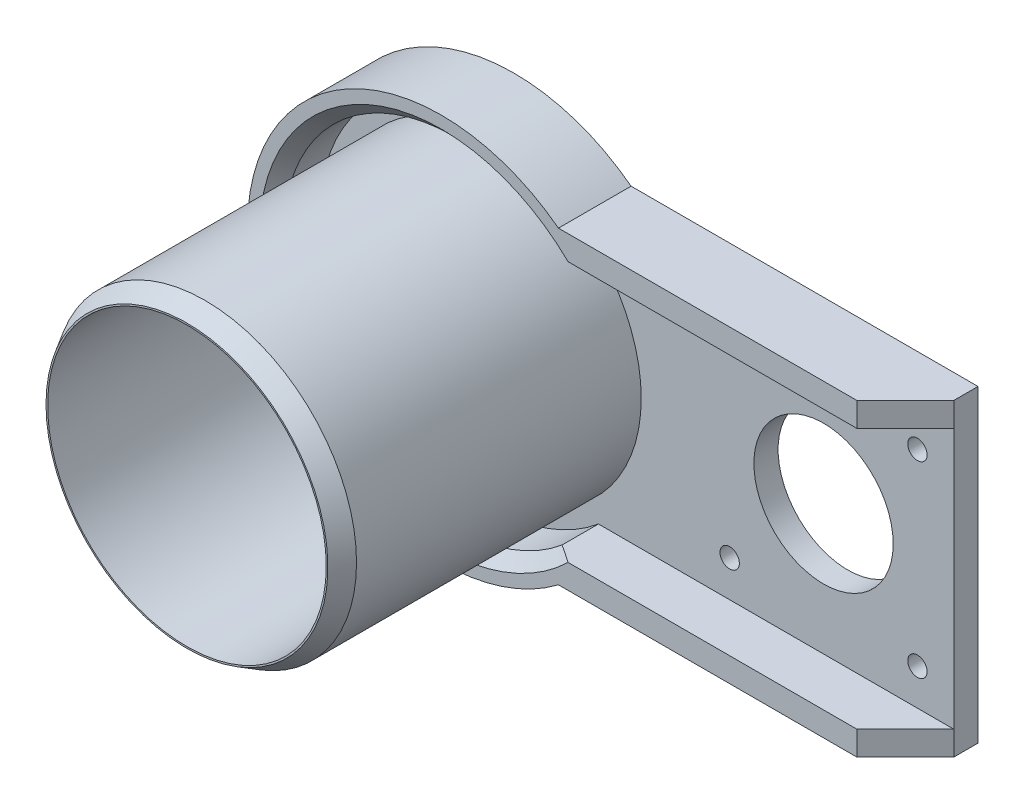
SolidWorks part; units mm, degrees
ref_plane "Front Plane" through (0, 0, 0) normal (0, 0, 1) x (1, 0, 0)
ref_plane "Top Plane" through (0, 0, 0) normal (0, 1, 0) x (1, 0, 0)
ref_plane "Right Plane" through (0, 0, 0) normal (1, 0, 0) x (0, 0, -1)
sketch "Sketch1" plane through (0, 0, 0) normal (0, 0, 1) x (1, 0, 0)
  line L0 (19.3326, 25.5) -> (76.6, 25.5)
  line L1 (76.6, 25.5) -> (76.6, -25.5)
  line L2 (76.6, -25.5) -> (19.3326, -25.5)
  circle A0 centre (0, 0) radius 6.55
  circle A1 centre (55.1, 0) radius 11.5
  arc A2 (19.3326, 25.5) -> (19.3326, -25.5) centre (0, 0) ccw
  circle A3 centre (39.6, 15.5) radius 1.6
  circle A4 centre (70.6, 15.5) radius 1.6
  circle A5 centre (70.6, -15.5) radius 1.6
  circle A6 centre (39.6, -15.5) radius 1.6
  point P10 (76.6, 0)
  point P19 (0, 0)
  point P20 (0, 0)
  point P21 (0, 0)
  dimension "D1" = 55.1
  dimension "D2" = 13.1
  dimension "D3" = 23
  dimension "D4" = 64
  dimension "D5" = 2
  dimension "D7" = 15.5
  dimension "D11" = 3.2
  dimension "D12" = 31
  dimension "D13" = 31
  dimension "D8" = 15.5
  dimension "D9" = 51
  dimension "D10" = 21.5
  dimension "D6" = 2
extrude "Boss-Extrude1" add sketch "Sketch1" along normal blind 4
sketch "Sketch2" plane through (0, 0, 4) normal (0, 0, 1) x (1, 0, 0)
  circle A0 centre (0, 0) radius 25
  circle A1 centre (0, 0) radius 23
  dimension "D1" = 50
  dimension "D2" = 46
extrude "Boss-Extrude2" add sketch "Sketch2" along normal blind 50
chamfer "Chamfer1" distance 3 angle 30 1 edges at (25, 0, 54) first distance on face at (25, 0, 54)
sketch "Sketch3" plane through (0, 0, 4) normal (0, 0, 1) x (1, 0, 0)
  line L0 (19.3326, -25.5) -> (76.6, -25.5) construction
  line L1 (76.6, 25.5) -> (19.3326, 25.5) construction
  line L2 (19.3326, -25.5) -> (76.6, -25.5)
  line L3 (76.6, 25.5) -> (19.3326, 25.5)
  line L4 (76.6, 21.5) -> (17.9374, 21.5)
  line L5 (17.9374, -21.5) -> (76.6, -21.5)
  line L6 (76.6, 25.5) -> (76.6, 21.5)
  line L7 (76.6, -25.5) -> (76.6, -21.5)
  arc A0 (19.3326, 25.5) -> (19.3326, -25.5) centre (0, 0) ccw construction
  arc A1 (19.3326, 25.5) -> (19.3326, -25.5) centre (0, 0) ccw
  arc A2 (17.9374, 21.5) -> (17.9374, -21.5) centre (0, 0) ccw
  dimension "D1" = 4
extrude "Boss-Extrude3" add sketch "Sketch3" along normal blind 8
chamfer "Chamfer4" distance 8 angle 45 2 edges at (76.6, -23.5, 12) (76.6, 23.5, 12)
chamfer "Chamfer5" distance 2 angle 45 1 edges at (-28, 0, 12)
